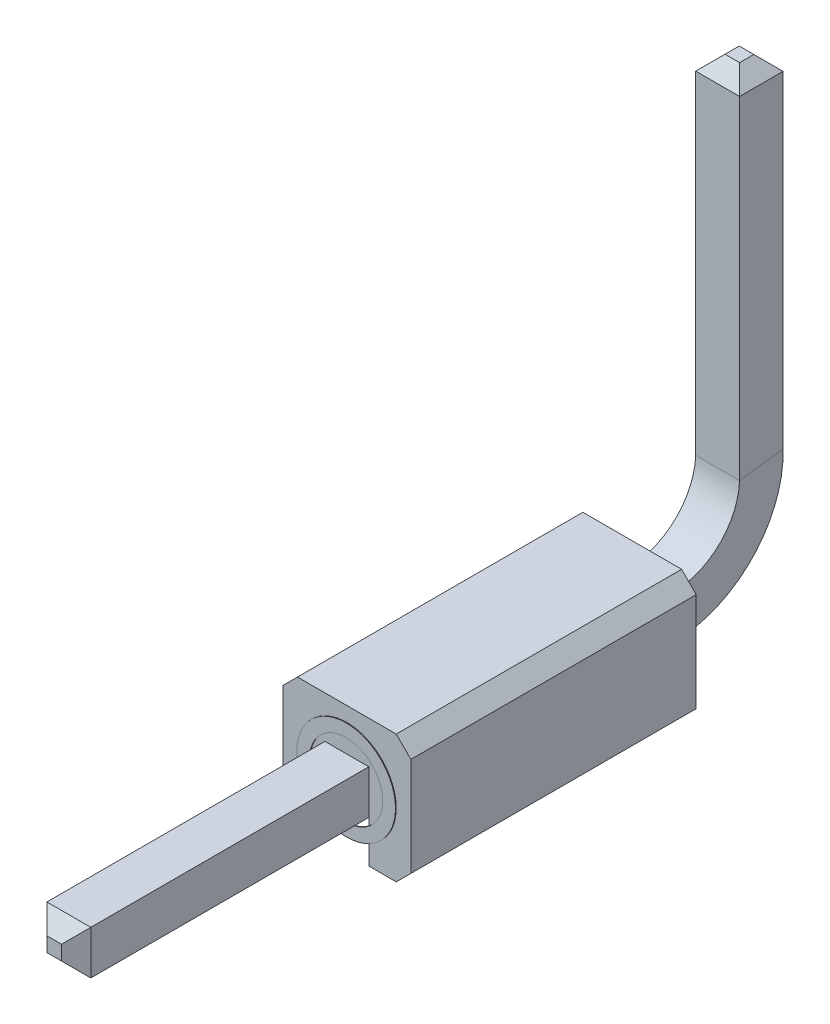
SolidWorks part; units mm, degrees
ref_plane "Plan de face" through (0, 0, 0) normal (0, 0, 1) x (1, 0, 0)
ref_plane "Plan de dessus" through (0, 0, 0) normal (0, 1, 0) x (1, 0, 0)
ref_plane "Plan de droite" through (0, 0, 0) normal (1, 0, 0) x (0, 0, -1)
sketch "Esquisse1" plane through (0, 0, 0) normal (0, 0, 1) x (1, 0, 0)
  line L0 (-0.675, 0.875) -> (-0.875, 0.675)
  line L1 (0.675, -0.875) -> (-0.675, -0.875)
  line L2 (0.875, -0.675) -> (0.875, 0.675)
  line L3 (0.675, 0.875) -> (-0.675, 0.875)
  line L4 (-0.875, -0.675) -> (-0.875, 0.675)
  line L5 (0.875, -0.875) -> (-0.875, 0.875) construction
  line L6 (0.875, 0.875) -> (-0.875, -0.875) construction
  line L7 (-0.675, -0.875) -> (-0.875, -0.675)
  line L8 (0.875, -0.675) -> (0.675, -0.875)
  line L9 (0.875, 0.675) -> (0.675, 0.875)
  line L11 (-0.3, 0.3) -> (0.3, 0.3)
  line L12 (-0.3, 0.3) -> (-0.3, -0.3)
  line L13 (-0.3, -0.3) -> (0.3, -0.3)
  line L14 (0.3, 0.3) -> (0.3, -0.3)
  line L15 (-0.3, 0.3) -> (0.3, -0.3) construction
  line L16 (-0.3, -0.3) -> (0.3, 0.3) construction
  point P0 (0, 0)
  point P14 (0, 0)
  dimension "D1" = 1.75
  dimension "D2" = 0.6
extrude "Boss.-Extru.1" add sketch "Esquisse1" along normal blind 2.8 and the other way blind 1.1
sketch "Esquisse2" plane through (0, 0, 2.8) normal (0, 0, 1) x (1, 0, 0)
  line L0 (-0.3, -0.3) -> (0.3, -0.3) construction
  line L1 (-0.3, -0.3) -> (0.3, -0.3)
  line L2 (-0.675, -0.875) -> (0.675, -0.875) construction
  line L3 (-0.3, -0.875) -> (0.3, -0.875)
  line L4 (-0.3, -0.3) -> (-0.3, -0.875)
  line L5 (0.3, -0.3) -> (0.3, -0.875)
extrude "Enlèv. mat.-Extru.1" cut sketch "Esquisse2" against normal blind 1
sketch "Esquisse3" plane through (0, 0, 2.8) normal (0, 0, 1) x (1, 0, 0)
  line L0 (0.3, -0.3) -> (-0.3, -0.3) construction
  line L1 (-0.3, 0.3) -> (-0.3, -0.875) construction
  line L2 (0.3, 0.3) -> (-0.3, 0.3) construction
  line L3 (0.3, -0.875) -> (0.3, 0.3) construction
  line L4 (0.3, -0.3) -> (-0.3, -0.3)
  line L5 (-0.3, 0.3) -> (-0.3, -0.3)
  line L6 (0.3, 0.3) -> (-0.3, 0.3)
  line L7 (0.3, -0.3) -> (0.3, 0.3)
extrude "Boss.-Extru.2" add sketch "Esquisse3" along normal blind 4 and the other way blind 4
sketch "Esquisse4" plane through (0, 0, 2.8) normal (0, 0, 1) x (1, 0, 0)
  circle A0 centre (0, 0) radius 0.5
  circle A1 centre (0, 0) radius 0.6746
  dimension "D1" = 1
extrude "Boss.-Extru.3" add sketch "Esquisse4" along normal blind 0.01
ref_plane "Plan1" through (0, 6, 0) normal (0, 1, 0) x (1, 0, 0)
sketch "Esquisse5" plane through (0, 6, 0) normal (0, 1, 0) x (1, 0, 0)
  line L3 (0.3, 2.2651) -> (-0.3, 2.2651)
  line L4 (0.3, 2.2651) -> (0.3, 2.8651)
  line L5 (0.3, 2.8651) -> (-0.3, 2.8651)
  line L6 (-0.3, 2.2651) -> (-0.3, 2.8651)
  line L7 (0.3, 2.2651) -> (-0.3, 2.8651) construction
  line L8 (0.3, 2.8651) -> (-0.3, 2.2651) construction
  point P2 (0, 2.5651)
  dimension "D1" = 0.6
  dimension "D2" = 0.6
sketch "Esquisse6" plane through (0, 0, -1.2) normal (0, 0, -1) x (-1, 0, 0)
  line L0 (0.3, 0.3) -> (-0.3, -0.3) construction
  line L1 (0.3, -0.3) -> (-0.3, 0.3) construction
  line L4 (-0.3, 0.3) -> (-0.3, -0.3)
  line L5 (-0.3, 0.3) -> (-0.3, -0.3)
  line L6 (-0.3, -0.3) -> (0.3, -0.3)
  line L7 (-0.3, -0.3) -> (0.3, -0.3)
  line L9 (0.3, -0.3) -> (0.3, 0.3)
  line L10 (0.3, -0.3) -> (0.3, 0.3)
  line L14 (0.3, 0.3) -> (-0.3, 0.3)
  line L15 (0.3, 0.3) -> (-0.3, 0.3)
  dimension "D1" = 0
sketch "Esquisse25" plane through (0, 0, 0) normal (1, 0, 0) x (0, 0, -1)
  line L0 (2.5651, 6) -> (2.5651, 1.1923)
  line L3 (1.2, -0.3) -> (1.2, 0.3) construction
  arc A0 (1.2, 0) -> (2.5651, 1.1923) centre (1.3618, 1.1923) ccw
  point P17 (1.2, 0)
sweep "Balayage1" add profiles "Esquisse6" path "Esquisse25"
extrude "Enlèv. mat.-Extru.2" cut sketch "Esquisse5" against normal blind 0.1 and the other way blind 0.1
chamfer "Chanfrein1" distance 0.2 angle 45 8 edges at (0, -0.3, 6.8) (-0.3, 0, 6.8) (0, 0.3, 6.8) (0.3, 0, 6.8) (0, 5.9, -2.2678) (-0.3, 5.9, -2.5651) (0, 5.9, -2.8624) (0.3, 5.9, -2.5651)
